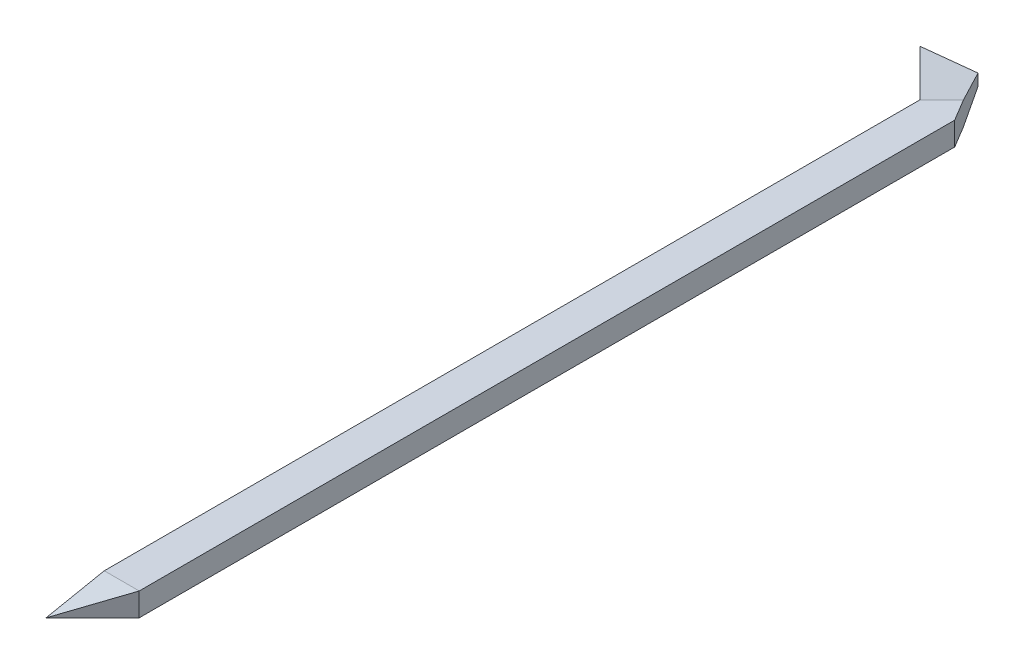
SolidWorks part; units mm, degrees
ref_plane "Front Plane" through (0, 0, 0) normal (0, 0, 1) x (1, 0, 0)
ref_plane "Top Plane" through (0, 0, 0) normal (0, 1, 0) x (1, 0, 0)
ref_plane "Right Plane" through (0, 0, 0) normal (1, 0, 0) x (0, 0, -1)
sketch "Sketch1" plane through (0, 0, 0) normal (0, 1, 0) x (1, 0, 0)
  line L0 (0, 101.6) -> (0, -101.6)
  line L1 (0, -101.6) -> (7.62, -88.9)
  line L2 (7.62, -88.9) -> (7.62, 88.9)
  line L3 (7.62, 88.9) -> (0, 101.6)
  line L4 (0, 101.6) -> (-12.7, 101.6)
  line L5 (-12.7, 101.6) -> (0, 88.9)
  line L6 (0, 88.9) -> (0, 101.6)
  point P4 (0, 0)
  point P8 (0, 0)
  dimension "D1" = 203.2
  dimension "D2" = 12.7
  dimension "D3" = 12.7
  dimension "D4" = 7.62
  dimension "D5" = 12.7
extrude "Boss-Extrude1" add sketch "Sketch1" along normal blind 5.08 contours L2 L3 L0 L1 | L4 L5 L0 region at (3.7253, 0, 0) region at (-4.2333, 0, -97.3667)
sketch "Sketch2" plane through (7.62, 0, 0) normal (1, 0, 0) x (0, 0, -1)
  line L0 (-88.9, 5.08) -> (-101.6, 2.54)
  line L1 (-101.6, 5.08) -> (-101.6, 0) construction
  line L2 (-101.6, 2.54) -> (-88.9, 0)
  line L3 (-88.9, 0) -> (-101.6, 0)
  line L4 (-101.6, 0) -> (-101.6, 2.54)
  line L5 (-101.6, 5.08) -> (-88.9, 5.08)
  line L6 (-101.6, 5.08) -> (-101.6, 2.54)
extrude "Cut-Extrude1" cut sketch "Sketch2" along normal through all both and the other way through all contours L5 L6 L0 | L4 L3 L2 region at (7.62, 0.8467, 97.3667) region at (7.62, 4.2333, 97.3667)
sketch "Sketch3" plane through (44.45, 0, -44.45) normal (-0.7071, 0, 0.7071) x (0.7071, 0, 0.7071)
  line L0 (-62.8618, 5.08) -> (-80.8223, 2.54)
  line L1 (-80.8223, 5.08) -> (-80.8223, 0) construction
  line L2 (-80.8223, 2.54) -> (-62.8618, 0)
  line L3 (-62.8618, 0) -> (-80.8223, 0)
  line L4 (-80.8223, 0) -> (-80.8223, 2.54)
  line L5 (-62.8618, 5.08) -> (-80.8223, 5.08)
  line L6 (-80.8223, 5.08) -> (-80.8223, 2.54)
  line M1 (-80.8223, 0) -> (-62.8618, 0)
  line M3 (-62.8618, 5.08) -> (-80.8223, 5.08)
  line M4 (-80.8223, 5.08) -> (-80.8223, 0)
extrude "Cut-Extrude2" cut sketch "Sketch3" against normal through all both and the other way through all contours L0 M3 M4 | L2 M4 M1 region at (-8.4667, 0.8467, -97.3667) region at (-8.4667, 4.2333, -97.3667)
